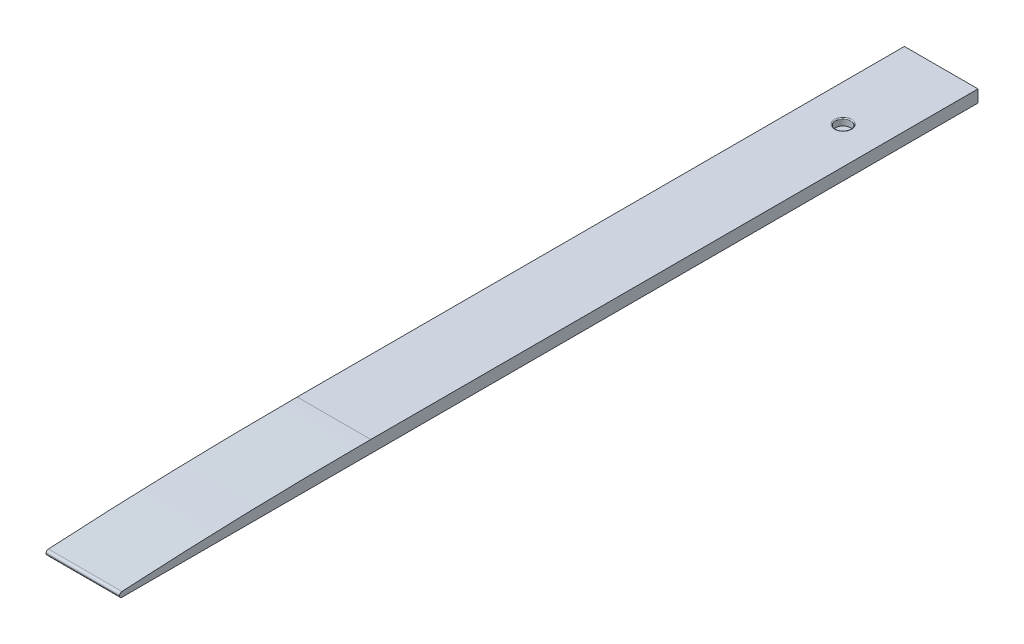
SolidWorks part; units mm, degrees
other "标注1"
sketch "草图6" plane through (0, 5, 350) normal (-0.6393, 0.5849, 0.4992) x (0.7619, 0.3939, 0.5141)
sketch "草图7" plane through (0, 5, 350) normal (-0.6393, 0.5849, 0.4992) x (0.7619, 0.3939, 0.5141)
ref_plane "前视基准面" through (0, 0, 0) normal (0, 0, 1) x (1, 0, 0)
ref_plane "上视基准面" through (0, 0, 0) normal (0, 1, 0) x (1, 0, 0)
ref_plane "右视基准面" through (0, 0, 0) normal (1, 0, 0) x (0, 0, -1)
other "Configuration Table"
sketch "草图1" plane through (0, 0, 0) normal (1, 0, 0) x (0, 0, -1)
  line L0 (0, 0) -> (-350, 0)
  line L5 (0, 5) -> (0, 0)
  line L6 (-300, 5) -> (0, 5)
  line L7 (-350, 0) -> (-350, 2)
  line L8 (-350, 2) -> (-300, 5)
  dimension "D1" = 350
  dimension "D2" = 5
  dimension "D3" = 2
  dimension "D7" = 50
extrude "凸台-拉伸1" add sketch "草图1" along normal blind 30
fillet "圆角1" radius 1750 1 edges at (15, 5, 300)
sketch "草图4" plane through (0, 5, 0) normal (0, 1, 0) x (1, 0, 0)
  line L0 (15, 0) -> (15, -40) construction
  line L1 (30, 0) -> (0, 0) construction
  line L2 (15, 0) -> (15, -40) construction
  circle A0 centre (15, -40) radius 3.1
  dimension "D2" = 6.2
  dimension "D1" = 40
extrude "切除-拉伸3" cut sketch "草图4" against normal blind 2.8
fillet "圆角4" radius 0.4 1 edges at (15, 5, 43.1)
sketch "草图5" plane through (0, 0, 0) normal (0, 0, -1) x (-1, 0, 0)
  line L0 (0, 0) -> (0, 5) construction
  line L1 (-25, 3.5) -> (-5, 3.5)
  line L2 (-25, 3.5) -> (-25, 1.5)
  line L3 (-25, 1.5) -> (-5, 1.5)
  line L4 (-5, 3.5) -> (-5, 1.5)
  line L5 (-30, 0) -> (-30, 5) construction
  line L6 (-30, 5) -> (0, 5) construction
  line L7 (-30, 0) -> (0, 0) construction
  dimension "D1" = 5
  dimension "D2" = 5
  dimension "D3" = 1.5
  dimension "D4" = 1.5
extrude "切除-拉伸4" cut sketch "草图5" against normal blind 25
fillet "圆角5" radius 1 2 edges at (15, 0, 350) (15, 2, 350)
fillet "圆角6" radius 1 2 edges at (15, 1.5, 0) (15, 3.5, 0)
